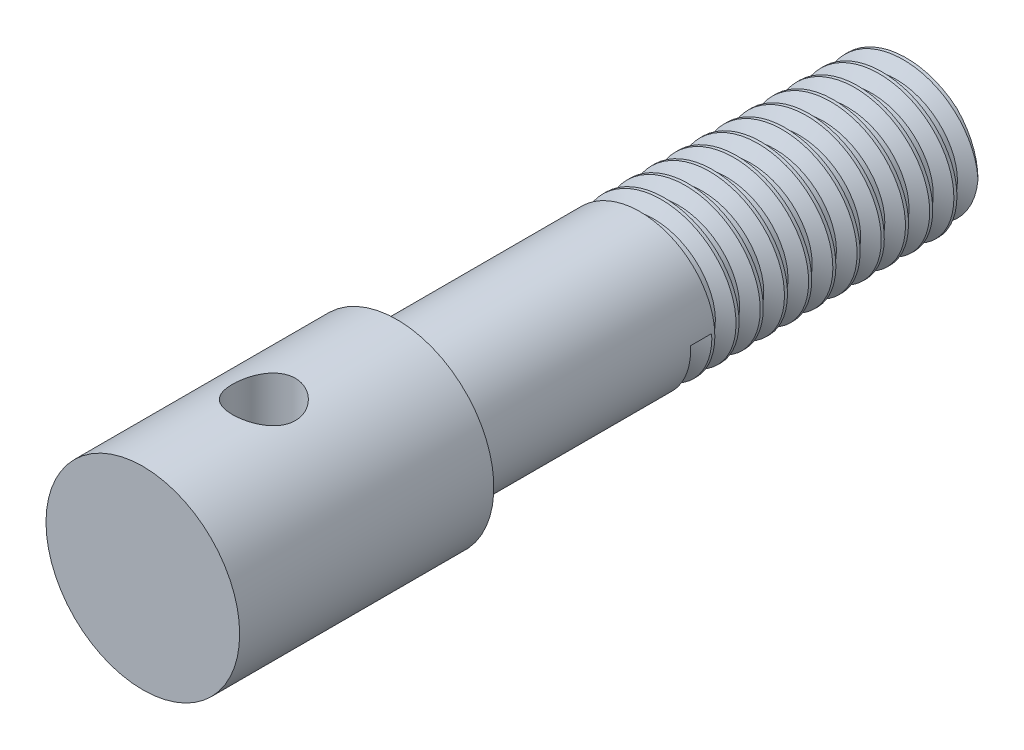
SolidWorks part; units mm, degrees
ref_plane "Alzado" through (0, 0, 0) normal (0, 0, 1) x (1, 0, 0)
ref_plane "Planta" through (0, 0, 0) normal (0, 1, 0) x (1, 0, 0)
ref_plane "Vista lateral" through (0, 0, 0) normal (1, 0, 0) x (0, 0, -1)
sketch "Croquis1" plane through (0, 0, 0) normal (0, 0, 1) x (1, 0, 0)
  circle A0 centre (0, 0) radius 4
  dimension "D1" = 8
extrude "Saliente-Extruir1" add sketch "Croquis1" along normal blind 35.5
ref_plane "Plano1" through (0, 4, 0) normal (0, 1, 0) x (1, 0, 0)
sketch "Croquis2" plane through (0, 4, 0) normal (0, 1, 0) x (1, 0, 0)
  line L0 (-4, -35.5) -> (4, -35.5) construction
  line L1 (-4, 0) -> (-4, -35.5) construction
  circle A0 centre (0, -30.5) radius 1.3
  dimension "D1" = 2.6
  dimension "D2" = 5
  dimension "D3" = 4
extrude "Cortar-Extruir1" cut sketch "Croquis2" against normal through all
sketch "Croquis3" plane through (0, 0, 0) normal (0, 0, -1) x (-1, 0, 0)
  circle A0 centre (0, 0) radius 3
  circle A2 centre (0, 0) radius 4
  dimension "D1" = 6
  dimension "D2" = 8
extrude "Cortar-Extruir2" cut sketch "Croquis3" against normal blind 25
thread "Rosca1" pitch 1 method cut profile "Perfil de rosca1" start angle 0, offset 0, length 15, pitch 1, diameter 6
ref_plane "Plano2" through (3, 0, 0) normal (0, -1, 0) x (1, 0, 0)
sketch "Perfil de rosca1" plane through (3, 0, 0) normal (0, -1, 0) x (1, 0, 0)
  line L0 (0, 0) -> (0, 1) construction
  line L11 (0, 0) -> (0, 0.875)
  line L12 (0, 0.875) -> (-0.5413, 0.5625)
  line L13 (-0.5413, 0.5625) -> (-0.5413, 0.3125)
  line L15 (-0.5413, 0.3125) -> (0, 0)
  line L17 (-0.5413, 0.4375) -> (0, 0.4375) construction
  point P2 (0, 0)
  dimension "Pitch" = 1
  dimension "Profile_Angle" = 60
  dimension "Profile_Land" = 0.25
  dimension "Profile_Height" = 0.5413
ref_plane "Plano3" through (0, 4, 0) normal (0, 1, 0) x (1, 0, 0)
sketch "Croquis8" plane through (0, 4, 0) normal (0, 1, 0) x (1, 0, 0)
  line L0 (-10, 0) -> (10, 0)
  line L1 (-10, 0) -> (-10, -4)
  line L2 (-10, -4) -> (10, -4)
  line L3 (10, -4) -> (10, 0)
  line L4 (3, 0) -> (-3, 0) construction
  line L5 (0, 0) -> (0, 3.2967) construction
  dimension "D1" = 4
  dimension "D2" = 20
extrude "Cortar-Extruir3" cut sketch "Croquis8" against normal through all
